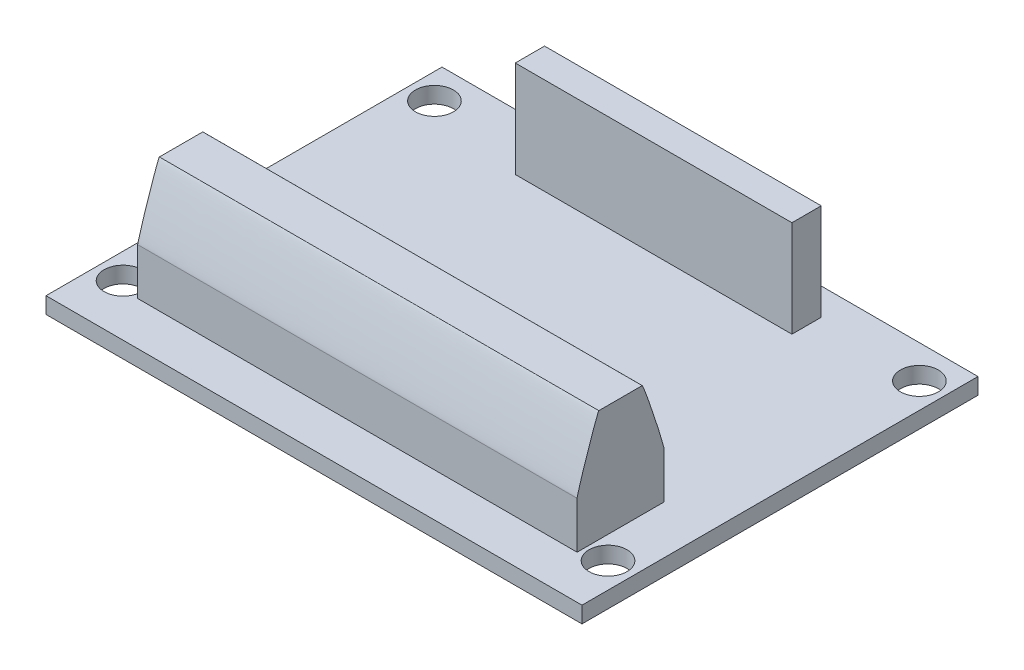
SolidWorks part; units mm, degrees
ref_plane "Front Plane" through (0, 0, 0) normal (0, 0, 1) x (1, 0, 0)
ref_plane "Top Plane" through (0, 0, 0) normal (0, 1, 0) x (1, 0, 0)
ref_plane "Right Plane" through (0, 0, 0) normal (1, 0, 0) x (0, 0, -1)
sketch "Sketch1" plane through (0, 0, 0) normal (0, 1, 0) x (1, 0, 0)
  line L1 (-125.8797, 3.2578) -> (-76.4797, 3.2578)
  line L2 (-125.8797, 3.2578) -> (-125.8797, -33.2422)
  line L3 (-125.8797, -33.2422) -> (-76.4797, -33.2422)
  line L4 (-76.4797, 3.2578) -> (-76.4797, -33.2422)
  line L5 (-121.4297, -21.2422) -> (-80.9297, -21.2422)
  line L6 (-121.4297, -21.2422) -> (-121.4297, -29.2422)
  line L7 (-121.4297, -29.2422) -> (-80.9297, -29.2422)
  line L8 (-80.9297, -21.2422) -> (-80.9297, -29.2422)
  line L9 (-113.9297, 0.7578) -> (-88.4297, 0.7578)
  line L10 (-113.9297, 0.7578) -> (-113.9297, -1.9422)
  line L11 (-113.9297, -1.9422) -> (-88.4297, -1.9422)
  line L12 (-88.4297, 0.7578) -> (-88.4297, -1.9422)
  circle A0 centre (-123.5297, 0.2078) radius 1.75
  circle A1 centre (-78.8297, 0.2078) radius 1.75
  circle A2 centre (-123.5297, -28.4922) radius 1.75
  circle A3 centre (-78.8297, -28.4922) radius 1.75
  point P12 (-101.1797, -29.2422)
  point P13 (-101.1797, -33.2422)
  point P22 (-101.1797, 0.7578)
  point P23 (-101.1797, 3.2578)
  dimension "D3" = 3.05
  dimension "D5" = 2.35
  dimension "D7" = 4.75
  dimension "D1" = 49.4
  dimension "D2" = 36.5
  dimension "D4" = 2.35
  dimension "D6" = 3.05
  dimension "D8" = 8
  dimension "D9" = 40.5
  dimension "D10" = 4
  dimension "D11" = 25.5
  dimension "D12" = 2.7
  dimension "D13" = 2.5
extrude "Boss-Extrude1" add sketch "Sketch1" along normal blind 1.5 contours A0 | A1 | L2 L3 L4 L1 | A2 | A3 region at (-123.5297, 0, -0.2078) region at (-78.8297, 0, -0.2078)
extrude "Boss-Extrude2" add sketch "Sketch1<3>" along normal blind 11.8 contours L8 L5 L6 L7 region at (-101.1797, 0, 25.2422)
sketch "Sketch1<3>" plane through (0, 0, 0) normal (0, 1, 0) x (1, 0, 0) same geometry as "Sketch1"
fillet "Fillet1" radius 2 1 edges at (-101.1797, 11.8, 21.2422) second distance 6 conic rho 0.05 first distance on face at (-101.1797, 11.8, 25.2422)
fillet "Fillet2" radius 6 1 edges at (-101.1797, 11.8, 29.2422) second distance 2 conic rho 0.05 first distance on face at (-101.1797, 6.65, 29.2422)
extrude "Boss-Extrude3" add sketch "Sketch1<4>" along normal blind 10.4 contours L12 L9 L10 L11 region at (-101.1797, 0, 0.5922)
sketch "Sketch1<4>" plane through (0, 0, 0) normal (0, 1, 0) x (1, 0, 0) same geometry as "Sketch1"
